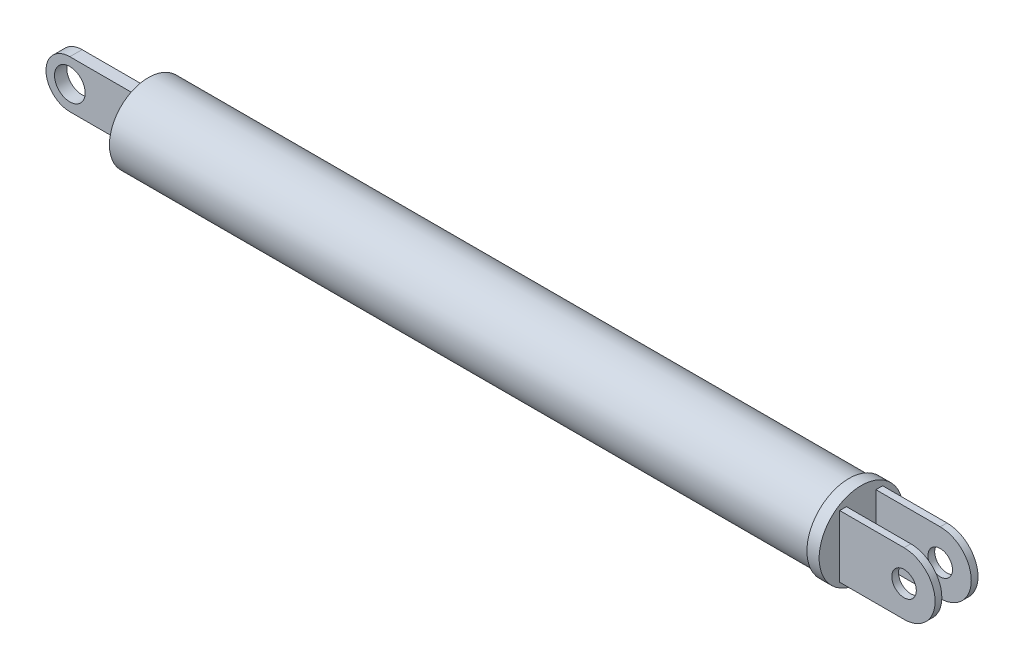
SolidWorks part; units mm, degrees
material "Cast Stainless Steel"
ref_plane "Front Plane" through (0, 0, 0) normal (0, 0, 1) x (1, 0, 0)
ref_plane "Top Plane" through (0, 0, 0) normal (0, 1, 0) x (1, 0, 0)
ref_plane "Right Plane" through (0, 0, 0) normal (1, 0, 0) x (0, 0, -1)
sketch "Sketch1" plane through (0, 0, 0) normal (1, 0, 0) x (0, 0, -1)
  circle A0 centre (0, 0) radius 12.7
  dimension "D1" = 25.4
extrude "Extrude1" add sketch "Sketch1" along normal blind 228.6
sketch "Sketch2" plane through (0, 0, 0) normal (0, 0, 1) x (1, 0, 0)
  line L0 (0, 0) -> (-32.8673, 0) construction
  line L1 (15.07, 0) -> (-15.07, 0) construction
  line L2 (0, 7.7781) -> (-23.6251, 7.7781)
  line L3 (0, 12.7) -> (0, -12.7) construction
  line L4 (0, -7.7781) -> (-23.6251, -7.7781)
  line L5 (0, 7.7781) -> (0, -7.7781)
  arc A0 (-23.6251, 7.7781) -> (-23.6251, -7.7781) centre (-23.6251, 0) ccw
  circle A1 centre (-23.6251, 0) radius 5
  dimension "D1" = 10
extrude "Extrude2" add sketch "Sketch2" along normal mid plane 4
sketch "Sketch3" plane through (228.6, 0, 0) normal (1, 0, 0) x (0, 0, -1)
  circle A2 centre (0, 0) radius 13.7
  circle A3 centre (0, 0) radius 13.7
  dimension "D1" = 1
extrude "Extrude3" add sketch "Sketch3" along normal blind 4
sketch "Sketch4" plane through (0, 0, 0) normal (0, 0, 1) x (1, 0, 0)
  line L0 (232.6, 10.1329) -> (253.6, 10.1329)
  line L1 (232.6, -13.7) -> (232.6, 13.7) construction
  line L2 (331.2897, 0) -> (364.956, 0) construction
  line L3 (232.6, -10.1329) -> (253.6, -10.1329)
  line L4 (232.6, 10.1329) -> (232.6, -10.1329)
  arc A0 (253.6, 10.1329) -> (253.6, -10.1329) centre (253.6, 0) cw
  circle A1 centre (253.6, 0) radius 4
  dimension "D1" = 8
  dimension "D2" = 21
extrude "Extrude4" add sketch "Sketch4" along normal mid plane 14
sketch "Sketch5" plane through (0, 0, 0) normal (0, 1, 0) x (1, 0, 0)
  line L0 (302.6802, 0) -> (363.3519, 0) construction
  line L1 (-15.07, 0) -> (15.07, 0) construction
  line L2 (232.6, -13.7) -> (232.6, 13.7) construction
  line L3 (232.6, 4.8012) -> (359.728, 4.8012)
  line L4 (232.6, 4.8012) -> (232.6, -4.8012)
  line L5 (232.6, -4.8012) -> (359.728, -4.8012)
  line L6 (359.728, 4.8012) -> (359.728, -4.8012)
  line L7 (359.728, 0) -> (232.6, 0) construction
extrude "Cut-Extrude1" cut sketch "Sketch5" against normal through all and the other way through all
sketch "Sketch6" plane through (0, 0, 0) normal (0, 0, 1) x (1, 0, 0)
  line L0 (82.3255, 0) -> (159.9018, 0) construction
  line L1 (15.07, 0) -> (-15.07, 0) construction
  line L3 (93.5607, 0) -> (141.979, 0)
  line L4 (93.5607, -102.8137) -> (93.5607, 102.8137)
  line L6 (141.979, -102.8137) -> (141.979, 102.8137)
  arc A0 (93.5607, 102.8137) -> (141.979, 102.8137) centre (117.7699, 102.8137) cw
  arc A1 (141.979, -102.8137) -> (93.5607, -102.8137) centre (117.7699, -102.8137) cw
  point P13 (93.5607, 102.8137)
extrude "Extrude5" [suppressed] add sketch "Sketch6" along normal blind 50 and the other way blind 40 contours A0 L4 L3 L6 | A1 L6 L3 L4
